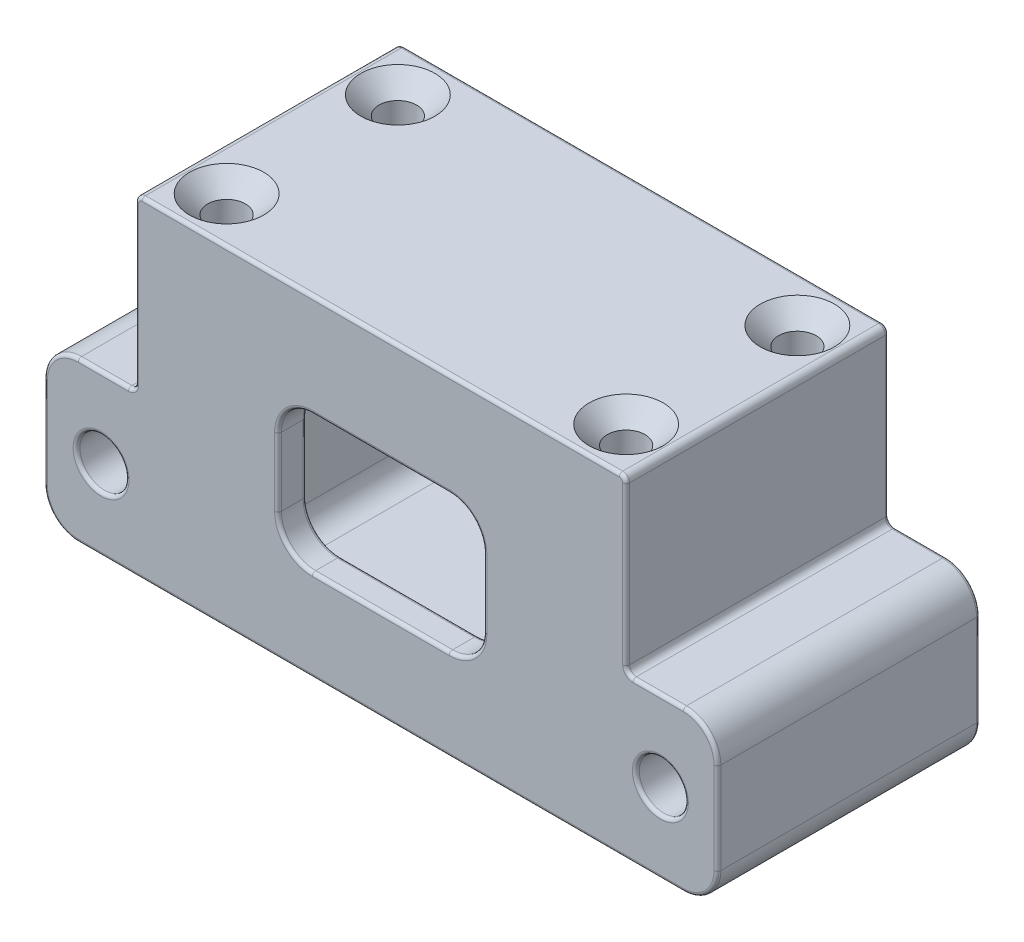
SolidWorks part; units mm, degrees
ref_plane "Front Plane" through (0, 0, 0) normal (0, 0, 1) x (1, 0, 0)
ref_plane "Top Plane" through (0, 0, 0) normal (0, 1, 0) x (1, 0, 0)
ref_plane "Right Plane" through (0, 0, 0) normal (1, 0, 0) x (0, 0, -1)
sketch "Sketch1" plane through (0, 0, 0) normal (0, 0, 1) x (1, 0, 0)
  line L1 (-21.5, 14.5) -> (21.5, 14.5)
  line L2 (-21.5, 14.5) -> (-21.5, -14.5)
  line L3 (-21.5, -14.5) -> (21.5, -14.5)
  line L4 (21.5, 14.5) -> (21.5, -14.5)
  line L5 (-21.5, 14.5) -> (21.5, -14.5) construction
  line L6 (-21.5, -14.5) -> (21.5, 14.5) construction
  point P0 (0, 0)
  dimension "D1" = 29
  dimension "D2" = 43
extrude "Boss-Extrude1" add sketch "Sketch1" along normal blind 23
sketch "Sketch2" plane through (0, 0, 0) normal (0, 0, -1) x (-1, 0, 0)
  line L1 (-15.5, 11.5) -> (15.5, 11.5)
  line L2 (-15.5, 11.5) -> (-15.5, -11.5)
  line L3 (-15.5, -11.5) -> (15.5, -11.5)
  line L4 (15.5, 11.5) -> (15.5, -11.5)
  line L5 (-15.5, 11.5) -> (15.5, -11.5) construction
  line L6 (-15.5, -11.5) -> (15.5, 11.5) construction
  point P0 (0, 0)
  dimension "D1" = 31
  dimension "D2" = 23
extrude "Cut-Extrude1" cut sketch "Sketch2" against normal blind 2
fillet "Fillet1" radius 2.5 2 edges at (-15.5, 11.5, 1) (15.5, 11.5, 1)
fillet "Fillet2" radius 2 2 edges at (-15.5, -11.5, 1) (15.5, -11.5, 1)
sketch "Sketch3" plane through (0, 0, 2) normal (0, 0, -1) x (-1, 0, 0)
  line L0 (0, 0) -> (0, 3.9669) construction
  line L1 (15.5, -9.5) -> (15.5, 9) construction
  line L2 (-13.5, 9.5) -> (13.5, 9.5)
  line L3 (-13.5, 9.5) -> (-13.5, -10.5)
  line L4 (-13.5, -10.5) -> (13.5, -10.5)
  line L5 (13.5, 9.5) -> (13.5, -10.5)
  line L6 (-13.5, 9.5) -> (13.5, -10.5) construction
  line L7 (-13.5, -10.5) -> (13.5, 9.5) construction
  line L8 (13, 11.5) -> (-13, 11.5) construction
  line L9 (-13.5, -11.5) -> (13.5, -11.5) construction
  point P3 (0, -0.5)
  dimension "D1" = 2
  dimension "D2" = 2
  dimension "D3" = 1
extrude "Cut-Extrude2" cut sketch "Sketch3" against normal blind 15.2
fillet "Fillet3" radius 2 4 edges at (-13.5, 9.5, 9.6) (-13.5, -10.5, 9.6) (13.5, -10.5, 9.6) (13.5, 9.5, 9.6)
sketch "Sketch4" plane through (0, 0, 17.2) normal (0, 0, -1) x (-1, 0, 0)
  line L0 (0, 0) -> (0, -0.5) construction
  line L1 (13.5, -8.5) -> (13.5, 7.5) construction
  line L2 (-15.5, 11.5) -> (15.5, 11.5)
  line L3 (-15.5, 11.5) -> (-15.5, -12.5)
  line L4 (-15.5, -12.5) -> (15.5, -12.5)
  line L5 (15.5, 11.5) -> (15.5, -12.5)
  line L6 (-15.5, 11.5) -> (15.5, -12.5) construction
  line L7 (-15.5, -12.5) -> (15.5, 11.5) construction
  line L8 (-11.5, -10.5) -> (11.5, -10.5) construction
  line L9 (11.5, 9.5) -> (-11.5, 9.5) construction
  dimension "D1" = 2
  dimension "D2" = 2
  dimension "D3" = 2
extrude "Cut-Extrude3" cut sketch "Sketch4" against normal blind 3.3
sketch "Sketch5" plane through (0, 0, 20.5) normal (0, 0, -1) x (-1, 0, 0)
  line L0 (0, 9.5) -> (0, -10.5) construction
  line L1 (11.5, 9.5) -> (-11.5, 9.5) construction
  line L2 (-11.5, -10.5) -> (11.5, -10.5) construction
  line L4 (-9, 5.5) -> (9, 5.5)
  line L5 (-9, 5.5) -> (-9, -6.5)
  line L6 (-9, -6.5) -> (9, -6.5)
  line L7 (9, 5.5) -> (9, -6.5)
  line L8 (-9, 5.5) -> (9, -6.5) construction
  line L9 (-9, -6.5) -> (9, 5.5) construction
  point P6 (0, -0.5)
  dimension "D1" = 12
  dimension "D2" = 18
extrude "Cut-Extrude4" cut sketch "Sketch5" against normal up to next
fillet "Fillet4" radius 4 4 edges at (-15.5, -12.5, 18.85) (15.5, -12.5, 18.85) (15.5, 11.5, 18.85) (-15.5, 11.5, 18.85)
fillet "Fillet5" radius 3 4 edges at (9, 5.5, 21.75) (9, -6.5, 21.75) (-9, -6.5, 21.75) (-9, 5.5, 21.75)
sketch "Sketch6" plane through (0, 14.5, 0) normal (0, 1, 0) x (1, 0, 0)
  line L0 (0, 0) -> (0, -12.9986) construction
  line L1 (21.5, 0) -> (-21.5, 0) construction
  line L2 (-17.5, 0) -> (-17.5, -23) construction
  line L3 (21.5, -23) -> (-21.5, -23) construction
  line L4 (-21.5, -23) -> (-21.5, 0) construction
  line L5 (17.5, 0) -> (17.5, -23) construction
  circle A0 centre (-17.5, -4) radius 1.65
  circle A1 centre (-17.5, -19) radius 1.65
  circle A2 centre (17.5, -19) radius 1.65
  circle A3 centre (17.5, -4) radius 1.65
  dimension "D1" = 3.3
  dimension "D3" = 4
  dimension "D4" = 4
  dimension "D2" = 4
extrude "Cut-Extrude5" cut sketch "Sketch6" against normal blind 36.3
sketch "Sketch8" plane through (0, -14.5, 0) normal (0, -1, 0) x (1, 0, 0)
  line L1 (-17.5, 15.5359) -> (-14.5, 17.2679)
  line L2 (-14.5, 17.2679) -> (-14.5, 20.7321)
  line L3 (-14.5, 20.7321) -> (-17.5, 22.4641)
  line L4 (-17.5, 22.4641) -> (-20.5, 20.7321)
  line L5 (-20.5, 20.7321) -> (-20.5, 17.2679)
  line L6 (-20.5, 17.2679) -> (-17.5, 15.5359)
  line L7 (-17.5, 7.4641) -> (-20.5, 5.7321)
  line L8 (-20.5, 5.7321) -> (-20.5, 2.2679)
  line L9 (-20.5, 2.2679) -> (-17.5, 0.5359)
  line L10 (-17.5, 0.5359) -> (-14.5, 2.2679)
  line L11 (-14.5, 2.2679) -> (-14.5, 5.7321)
  line L12 (-14.5, 5.7321) -> (-17.5, 7.4641)
  line L13 (17.5, 7.4641) -> (14.5, 5.7321)
  line L14 (14.5, 5.7321) -> (14.5, 2.2679)
  line L15 (14.5, 2.2679) -> (17.5, 0.5359)
  line L16 (17.5, 0.5359) -> (20.5, 2.2679)
  line L17 (20.5, 2.2679) -> (20.5, 5.7321)
  line L18 (20.5, 5.7321) -> (17.5, 7.4641)
  line L19 (17.5, 15.5359) -> (20.5, 17.2679)
  line L20 (20.5, 17.2679) -> (20.5, 20.7321)
  line L21 (20.5, 20.7321) -> (17.5, 22.4641)
  line L22 (17.5, 22.4641) -> (14.5, 20.7321)
  line L23 (14.5, 20.7321) -> (14.5, 17.2679)
  line L24 (14.5, 17.2679) -> (17.5, 15.5359)
  circle A0 centre (-17.5, 19) radius 3 construction
  circle A1 centre (-17.5, 4) radius 3 construction
  circle A2 centre (17.5, 4) radius 3 construction
  circle A3 centre (17.5, 19) radius 3 construction
  dimension "D1" = 6
extrude "Cut-Extrude6" cut sketch "Sketch8" against normal blind 3
chamfer "Chamfer1" distance 1.6 angle 45 4 edges at (17.5, 14.5, 2.35) (17.5, 14.5, 17.35) (-17.5, 14.5, 20.65) (-17.5, 14.5, 5.65)
sketch "Sketch9" plane through (21.5, 0, 0) normal (1, 0, 0) x (0, 0, -1)
  line L0 (0, -14.5) -> (0, 14.5) construction
  line L1 (-23, -14.5) -> (0, -14.5)
  line L2 (-23, -14.5) -> (-23, -0.5)
  line L3 (-23, -0.5) -> (0, -0.5)
  line L4 (0, -14.5) -> (0, -0.5)
  line L5 (-23, -14.5) -> (0, -14.5) construction
  dimension "D1" = 14
extrude "Boss-Extrude2" add sketch "Sketch9" along normal blind 8
mirror "Mirror1" about plane through (0, 0, 0) normal (1, 0, 0) of "Boss-Extrude2"
sketch "Sketch10" plane through (0, 0, 23) normal (0, 0, 1) x (1, 0, 0)
  line L0 (-29.5, -7.5) -> (29.5, -7.5) construction
  line L1 (-29.5, -0.5) -> (-29.5, -14.5) construction
  line L2 (29.5, -0.5) -> (29.5, -14.5) construction
  line L3 (0, 0) -> (0, -7.5) construction
  circle A0 centre (-24.5, -7.5) radius 2.15
  circle A1 centre (24.5, -7.5) radius 2.15
  dimension "D1" = 5
  dimension "D2" = 4.3
extrude "Cut-Extrude7" cut sketch "Sketch10" against normal blind 37
sketch "Sketch11" plane through (0, 0, 0) normal (0, 0, -1) x (-1, 0, 0)
  line L1 (-24.5, -11.6569) -> (-20.9, -9.5785)
  line L2 (-20.9, -9.5785) -> (-20.9, -5.4215)
  line L3 (-20.9, -5.4215) -> (-24.5, -3.3431)
  line L4 (-24.5, -3.3431) -> (-28.1, -5.4215)
  line L5 (-28.1, -5.4215) -> (-28.1, -9.5785)
  line L6 (-28.1, -9.5785) -> (-24.5, -11.6569)
  line L7 (24.5, -11.6569) -> (28.1, -9.5785)
  line L8 (28.1, -9.5785) -> (28.1, -5.4215)
  line L9 (28.1, -5.4215) -> (24.5, -3.3431)
  line L10 (24.5, -3.3431) -> (20.9, -5.4215)
  line L11 (20.9, -5.4215) -> (20.9, -9.5785)
  line L12 (20.9, -9.5785) -> (24.5, -11.6569)
  circle A0 centre (-24.5, -7.5) radius 3.6 construction
  circle A1 centre (24.5, -7.5) radius 3.6 construction
  dimension "D1" = 7.2
extrude "Cut-Extrude8" cut sketch "Sketch11" against normal blind 4
fillet "Fillet6" radius 3 4 edges at (-29.5, -14.5, 11.5) (-29.5, -0.5, 11.5) (29.5, -0.5, 11.5) (29.5, -14.5, 11.5)
fillet "Fillet7" radius 0.6 4 edges at (21.5, 14.5, 11.5) (-21.5, 14.5, 11.5) (-21.5, -0.5, 11.5) (21.5, -0.5, 11.5)
fillet "Fillet8" radius 0.3 86 edges at (8.1213, 4.6213, 20.5) (0, 5.5, 20.5) (-8.1213, 4.6213, 20.5) (-9, -0.5, 20.5) (-8.1213, -5.6213, 20.5) (0, -6.5, 20.5) (8.1213, -5.6213, 20.5) (12.9142, 8.9142, 17.2) (0, 9.5, 17.2) (-12.9142, 8.9142, 17.2) (-13.5, -0.5, 17.2) (-12.9142, -9.9142, 17.2) (0, -10.5, 17.2) (12.9142, -9.9142, 17.2) (12.9142, -9.9142, 2) (13.5, -0.5, 2) (12.9142, 8.9142, 2) (0, 9.5, 2) (-12.9142, 8.9142, 2) (-13.5, -0.5, 2) (-12.9142, -9.9142, 2) (-21.3243, 14.3243, 0) (-21.5, 7, 0) (-21.6757, -0.3243, 0) (-24.3, -0.5, 0) (-28.6213, -1.3787, 0) (-29.5, -7.5, 0) (-28.6213, -13.6213, 0) (0, -14.5, 0) (28.6213, -13.6213, 0) (29.5, -7.5, 0) (28.6213, -1.3787, 0) (24.3, -0.5, 0) (21.6757, -0.3243, 0) (21.5, 7, 0) (21.3243, 14.3243, 0) (0, 14.5, 0) (14.7678, 10.7678, 0) (15.5, -0.25, 0) (14.9142, -10.9142, 0) (0, -11.5, 0) (-14.9142, -10.9142, 0) (-15.5, -0.25, 0) (-14.7678, 10.7678, 0) (0, 11.5, 0) (-28.1, -7.5, 0) (-26.3, -4.3823, 0) (-22.7, -4.3823, 0) (-20.9, -7.5, 0) (-22.7, -10.6177, 0) (-26.3, -10.6177, 0) (20.9, -7.5, 0) (22.7, -4.3823, 0) (26.3, -4.3823, 0) (28.1, -7.5, 0) (26.3, -10.6177, 0) (22.7, -10.6177, 0) (21.6757, -0.3243, 23) (24.3, -0.5, 23) (28.6213, -1.3787, 23) (29.5, -7.5, 23) (28.6213, -13.6213, 23) (0, -14.5, 23) (-28.6213, -13.6213, 23) (-29.5, -7.5, 23) (-28.6213, -1.3787, 23) (-24.3, -0.5, 23) (-21.6757, -0.3243, 23) (-21.5, 7, 23) (-21.3243, 14.3243, 23) (0, 14.5, 23) (21.3243, 14.3243, 23) (21.5, 7, 23) (8.1213, -5.6213, 23) (9, -0.5, 23) (8.1213, 4.6213, 23) (0, 5.5, 23) (-8.1213, 4.6213, 23) (-9, -0.5, 23) (-8.1213, -5.6213, 23) (0, -6.5, 23) (22.35, -7.5, 23) (-22.35, -7.5, 23) (9, -0.5, 20.5) (13.5, -0.5, 17.2) (0, -10.5, 2)
sketch "Sketch12" plane through (0, 0, 0) normal (0, 1, 0) x (1, 0, 0)
  line L1 (-38.5237, 7.6107) -> (40.0356, 7.6107)
  line L2 (-38.5237, 7.6107) -> (-38.5237, -28.6754)
  line L3 (-38.5237, -28.6754) -> (40.0356, -28.6754)
  line L4 (40.0356, 7.6107) -> (40.0356, -28.6754)
extrude "Cut-Extrude9" [suppressed] cut sketch "Sketch12" against normal blind 18 from offset 1
fillet "Fillet9" [suppressed] radius 0.3
fillet "Fillet10" [suppressed] radius 0.3
